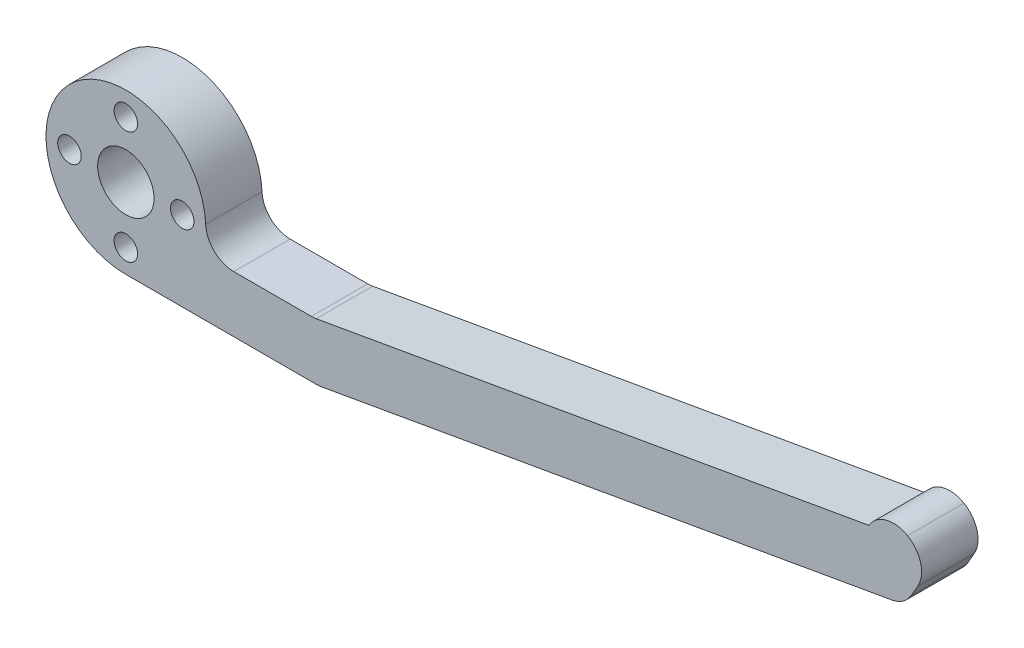
SolidWorks part; units mm, degrees
ref_plane "Plan de face" through (0, 0, 0) normal (0, 0, 1) x (1, 0, 0)
ref_plane "Plan de dessus" through (0, 0, 0) normal (0, 1, 0) x (1, 0, 0)
ref_plane "Plan de droite" through (0, 0, 0) normal (1, 0, 0) x (0, 0, -1)
sketch "Esquisse1" plane through (0, 0, 0) normal (0, 0, 1) x (1, 0, 0)
  circle A0 centre (0, 0) radius 8.5
  dimension "D1" = 17
extrude "Boss.-Extru.1" add sketch "Esquisse1" along normal blind 6
sketch "Esquisse2" plane through (0, 0, 6) normal (0, 0, 1) x (1, 0, 0)
  line L0 (0, -8.5) -> (20, -8.5)
  line L1 (20, -8.5) -> (20, -2.5)
  line L2 (20, -2.5) -> (8.124, -2.5)
  line L3 (8.124, -2.5) -> (0, -8.5)
  line L4 (0, -8.5) -> (0, 0) construction
  circle A0 centre (0, 0) radius 8.5 construction
  dimension "D1" = 20
  dimension "D2" = 6
extrude "Boss.-Extru.2" add sketch "Esquisse2" against normal up to surface (6 mm away) up to face at (8.5, 0, 0)
sketch "Esquisse3" plane through (0, 0, 6) normal (0, 0, 1) x (1, 0, 0)
  line L0 (20, -2.5) -> (79.0885, 7.9189)
  line L1 (79.0885, 7.9189) -> (80.1304, 2.01)
  line L2 (80.1304, 2.01) -> (20.5249, -8.5)
  line L3 (20.5249, -8.5) -> (20, -8.5)
  line L4 (20, -8.5) -> (20, -2.5)
  line L5 (20, -2.5) -> (8.124, -2.5) construction
  dimension "D1" = 170
  dimension "D2" = 60
extrude "Boss.-Extru.3" add sketch "Esquisse3" against normal up to vertex (6 mm away) up to point (8.124, -2.5, 0)
sketch "Esquisse5" plane through (0, 0, 6) normal (0, 0, 1) x (1, 0, 0)
  line L0 (80.1304, 2.01) -> (82.8857, 2.4959)
  line L1 (82.8857, 2.4959) -> (85.7846, 7.517)
  line L2 (85.7846, 7.517) -> (80.5885, 10.517)
  line L3 (80.5885, 10.517) -> (79.0885, 7.9189)
  line L4 (79.0885, 7.9189) -> (80.1304, 2.01)
  line L5 (20.5249, -8.5) -> (80.1304, 2.01) construction
  line L6 (79.0885, 7.9189) -> (20, -2.5) construction
  dimension "D1" = 3
  dimension "D2" = 130
extrude "Boss.-Extru.4" add sketch "Esquisse5" against normal up to vertex (6 mm away) up to point (79.0885, 7.9189, 0)
sketch "Esquisse4" plane through (0, 0, 6) normal (0, 0, 1) x (1, 0, 0)
  line L0 (0, 0) -> (-6, 0) construction
  circle A0 centre (0, 0) radius 3
  circle A1 centre (-6, 0) radius 1.25
  circle A2 centre (0, 6) radius 1.25
  circle A3 centre (6, 0) radius 1.25
  circle A4 centre (0, -6) radius 1.25
  point P14 (0, 0)
  dimension "D1" = 2.5
  dimension "D2" = 6
  dimension "D3" = 6
  dimension "D4" = 4
extrude "Enlèv. mat.-Extru.1" cut sketch "Esquisse4" against normal through all both and the other way through all
fillet "Congé1" radius 3 6 edges at (20.5249, -8.5, 3) (82.8857, 2.4959, 3) (85.7846, 7.517, 3) (80.5885, 10.517, 3) (20, -2.5, 3) (8.124, -2.5, 3)
